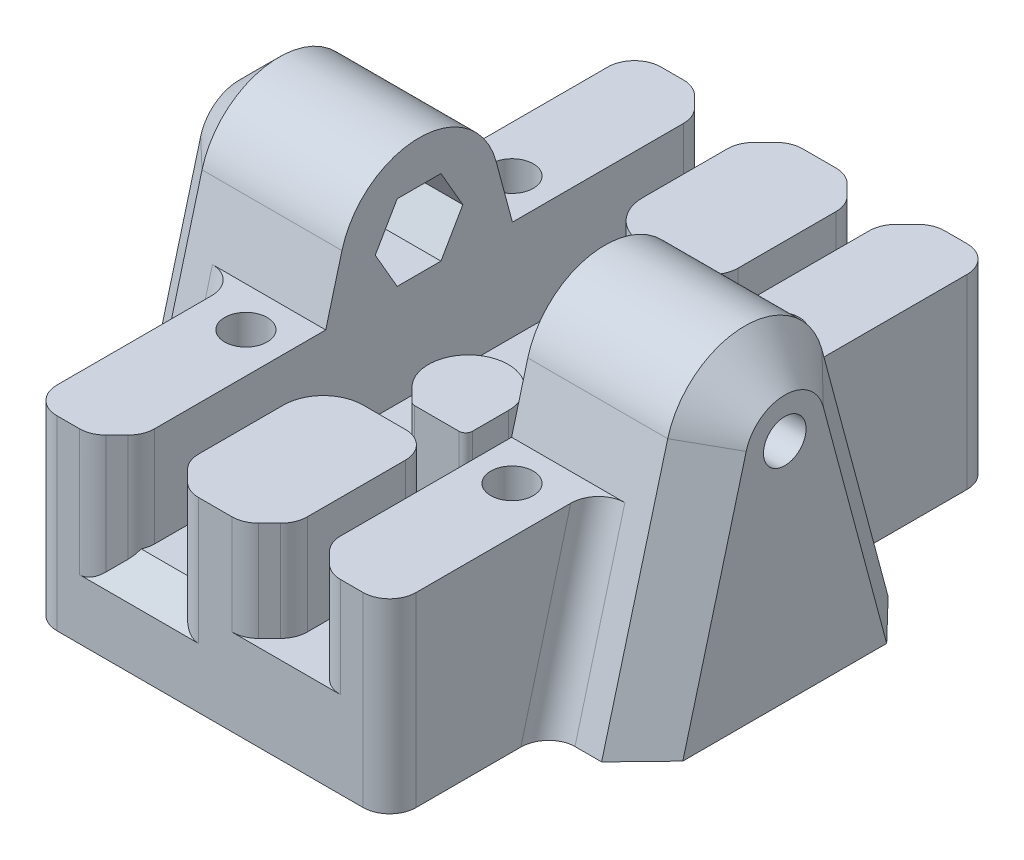
SolidWorks part; units mm, degrees
ref_plane "Front Plane" through (0, 0, 0) normal (0, 0, 1) x (1, 0, 0)
ref_plane "Top Plane" through (0, 0, 0) normal (0, 1, 0) x (1, 0, 0)
ref_plane "Right Plane" through (0, 0, 0) normal (1, 0, 0) x (0, 0, -1)
sketch "Sketch1" plane through (0, 0, 0) normal (0, 1, 0) x (1, 0, 0)
  line L1 (-12, -22.7) -> (12, -22.7)
  line L2 (-13.5, -21.2) -> (-13.5, 21.2)
  line L3 (-12, 22.7) -> (12, 22.7)
  line L4 (13.5, -21.2) -> (13.5, 21.2)
  line L5 (-13.5, -22.7) -> (13.5, 22.7) construction
  line L6 (-13.5, 22.7) -> (13.5, -22.7) construction
  arc A0 (-13.5, 21.2) -> (-12, 22.7) centre (-12, 21.2) cw
  arc A1 (12, 22.7) -> (13.5, 21.2) centre (12, 21.2) cw
  arc A2 (12, -22.7) -> (13.5, -21.2) centre (12, -21.2) ccw
  arc A3 (-12, -22.7) -> (-13.5, -21.2) centre (-12, -21.2) cw
  point P0 (0, 0)
  dimension "D3" = 1.5
  dimension "D1" = 27
  dimension "D2" = 45.4
sketch "Sketch3" plane through (0, 0, 0) normal (1, 0, 0) x (0, 0, -1)
  line L0 (55, 0) -> (-55, 0) construction
  line L1 (0, 55) -> (0, -55) construction
  circle A0 centre (0, 4) radius 5
  dimension "D1" = 10
  dimension "D2" = 4
sketch "Sketch27" plane through (0, 0, 0) normal (0, 1, 0) x (1, 0, 0)
  line L6 (4.6213, 8.6) -> (1.2858, 8.6)
  line L7 (0.9322, 8.4536) -> (0, 7.5213)
  line L8 (5.1213, 5.4) -> (5.1213, 8.1)
  line L12 (1.2858, -8.6) -> (4.6213, -8.6)
  line L13 (5.1213, -8.1) -> (5.1213, -5.4)
  line L14 (0, -7.5213) -> (0.9322, -8.4536)
  line L28 (2.985, -10.5) -> (1.317, -10.5)
  line L29 (1.317, -10.5) -> (1.317, -12.5)
  line L30 (1.317, -12.5) -> (2.485, -12.5)
  line L31 (2.485, -12.5) -> (2.485, -20.5)
  line L32 (2.485, -20.5) -> (-3.683, -20.5)
  line L33 (-3.683, -20.5) -> (-3.683, -22.7)
  line L34 (-3.683, -22.7) -> (4.485, -22.7)
  line L35 (4.485, -22.7) -> (4.485, -12)
  line L44 (6.985, -20.5) -> (6.985, -22.7)
  line L45 (6.985, -22.7) -> (12, -22.7)
  line L46 (13.5, -21.2) -> (13.5, -5.35)
  line L47 (13.5, -5.35) -> (11.3, -5.35)
  line L48 (11.3, -5.35) -> (11.3, -6.4293)
  line L49 (6.985, -7.687) -> (6.985, -12.313)
  line L50 (11.3, -13.5707) -> (11.3, -20.5)
  line L51 (11.3, -20.5) -> (6.985, -20.5)
  line L60 (6.985, 12.313) -> (6.985, 7.687)
  line L61 (11.3, 6.4293) -> (11.3, 5.35)
  line L62 (11.3, 5.35) -> (13.5, 5.35)
  line L63 (13.5, 5.35) -> (13.5, 21.2)
  line L64 (12, 22.7) -> (6.985, 22.7)
  line L65 (6.985, 22.7) -> (6.985, 20.5)
  line L66 (6.985, 20.5) -> (11.3, 20.5)
  line L67 (11.3, 20.5) -> (11.3, 13.5707)
  line L68 (1.317, 12.5) -> (-3.683, 12.5)
  line L69 (-3.683, 12.5) -> (-3.683, 10.5)
  line L70 (-3.683, 10.5) -> (1.317, 10.5)
  line L71 (1.317, 10.5) -> (1.317, 12.5)
  line L84 (2.485, 12.5) -> (1.317, 12.5)
  line L85 (1.317, 12.5) -> (1.317, 10.5)
  line L86 (1.317, 10.5) -> (2.985, 10.5)
  line L87 (4.485, 12) -> (4.485, 22.7)
  line L88 (4.485, 22.7) -> (-3.683, 22.7)
  line L89 (-3.683, 22.7) -> (-3.683, 20.5)
  line L90 (-3.683, 20.5) -> (2.485, 20.5)
  line L91 (2.485, 20.5) -> (2.485, 12.5)
  line L92 (1.317, -10.5) -> (-3.683, -10.5)
  line L93 (-3.683, -10.5) -> (-3.683, -12.5)
  line L94 (-3.683, -12.5) -> (1.317, -12.5)
  line L95 (1.317, -12.5) -> (1.317, -10.5)
  line L110 (-6.985, -12.5) -> (-6.985, -7.687)
  line L111 (-11.3, -6.4293) -> (-11.3, -5.35)
  line L112 (-11.3, -5.35) -> (-13.5, -5.35)
  line L113 (-13.5, -5.35) -> (-13.5, -21.2)
  line L114 (-12, -22.7) -> (-6.985, -22.7)
  line L115 (-6.985, -22.7) -> (-6.985, -20.5)
  line L116 (-6.985, -20.5) -> (-11.3, -20.5)
  line L117 (-11.3, -20.5) -> (-11.3, -13.5707)
  line L118 (-7.1382, -12.5) -> (-6.985, -12.5)
  line L128 (-6.985, 20.5) -> (-6.985, 22.7)
  line L129 (-6.985, 22.7) -> (-12, 22.7)
  line L130 (-13.5, 21.2) -> (-13.5, 5.35)
  line L131 (-13.5, 5.35) -> (-11.3, 5.35)
  line L132 (-11.3, 5.35) -> (-11.3, 6.4293)
  line L133 (-6.985, 7.687) -> (-6.985, 12.5)
  line L134 (-6.985, 12.5) -> (-7.1382, 12.5)
  line L135 (-11.3, 13.5707) -> (-11.3, 20.5)
  line L136 (-11.3, 20.5) -> (-6.985, 20.5)
  arc A2 (4.485, -12) -> (2.985, -10.5) centre (2.985, -12) ccw
  arc A6 (1.2858, 8.6) -> (0.9322, 8.4536) centre (1.2858, 8.1) ccw
  arc A7 (0, 7.5213) -> (5.1213, 5.4) centre (2.1213, 5.4) ccw
  arc A8 (5.1213, 8.1) -> (4.6213, 8.6) centre (4.6213, 8.1) ccw
  arc A12 (4.6213, -8.6) -> (5.1213, -8.1) centre (4.6213, -8.1) ccw
  arc A13 (5.1213, -5.4) -> (0, -7.5213) centre (2.1213, -5.4) ccw
  arc A14 (0.9322, -8.4536) -> (1.2858, -8.6) centre (1.2858, -8.1) ccw
  arc A16 (2.985, 10.5) -> (4.485, 12) centre (2.985, 12) ccw
  arc A20 (12, -22.7) -> (13.5, -21.2) centre (12, -21.2) ccw
  arc A21 (11.3, -6.4293) -> (6.985, -7.687) centre (10, -10) ccw
  arc A22 (6.985, -12.313) -> (11.3, -13.5707) centre (10, -10) ccw
  arc A26 (6.985, 7.687) -> (11.3, 6.4293) centre (10, 10) ccw
  arc A27 (13.5, 21.2) -> (12, 22.7) centre (12, 21.2) ccw
  arc A28 (11.3, 13.5707) -> (6.985, 12.313) centre (10, 10) ccw
  arc A34 (-6.985, -7.687) -> (-11.3, -6.4293) centre (-10, -10) ccw
  arc A35 (-13.5, -21.2) -> (-12, -22.7) centre (-12, -21.2) ccw
  arc A36 (-11.3, -13.5707) -> (-7.1382, -12.5) centre (-10, -10) ccw
  arc A40 (-12, 22.7) -> (-13.5, 21.2) centre (-12, 21.2) ccw
  arc A41 (-11.3, 6.4293) -> (-6.985, 7.687) centre (-10, 10) ccw
  arc A42 (-7.1382, 12.5) -> (-11.3, 13.5707) centre (-10, 10) ccw
sketch "Sketch29" plane through (0, 0, 0) normal (0, 1, 0) x (1, 0, 0)
  line L1 (-13.5, 22.7) -> (13.5, 22.7)
  line L2 (-13.5, 22.7) -> (-13.5, -22.7)
  line L3 (-13.5, -22.7) -> (13.5, -22.7)
  line L4 (13.5, 22.7) -> (13.5, -22.7)
extrude "Boss-Extrude1" add sketch "Sketch29" along normal blind 6.5
fillet "Fillet1" radius 2 4 edges at (-13.5, 3.25, -22.7) (13.5, 3.25, -22.7) (13.5, 3.25, 22.7) (-13.5, 3.25, 22.7)
sketch "Sketch30" plane through (0, 6.5, 0) normal (0, 1, 0) x (1, 0, 0)
  line L5 (4.485, -22.7) -> (4.485, -12) construction
  line L9 (-3.683, -10.5) -> (-3.683, -12.5) construction
  line L12 (-13.5, 0) -> (13.5, 0) construction
  line L13 (4.485, 22.7) -> (4.485, 10.5)
  line L14 (-11.5, -22.7) -> (11.5, -22.7) construction
  line L15 (-3.683, 10.5) -> (4.485, 10.5)
  line L16 (-3.683, 10.5) -> (-3.683, 22.7)
  line L17 (4.485, -10.5) -> (-3.683, -10.5)
  line L18 (6.985, 22.7) -> (6.985, -22.7)
  line L19 (-6.985, 22.7) -> (-6.985, -22.7)
  line L20 (-3.683, -22.7) -> (4.485, -22.7)
  line L21 (6.985, -22.7) -> (11.5, -22.7)
  line L22 (4.485, 22.7) -> (-3.683, 22.7)
  line L23 (-6.985, 22.7) -> (-11.5, 22.7)
  line L24 (4.6213, 8.6) -> (1.2858, 8.6) construction
  line L25 (0.9322, 8.4536) -> (0, 7.5213) construction
  line L26 (5.1213, 5.4) -> (5.1213, 8.1) construction
  line L27 (0, -7.5213) -> (0.9322, -8.4536) construction
  line L28 (1.2858, -8.6) -> (4.6213, -8.6) construction
  line L29 (5.1213, -8.1) -> (5.1213, -5.4) construction
  line L69 (4.485, -22.7) -> (4.485, -10.5)
  line L73 (-3.683, -10.5) -> (-3.683, -22.7)
  line L80 (11.5, 22.7) -> (-11.5, 22.7)
  line L81 (-13.5, 20.7) -> (-13.5, -20.7)
  line L82 (-11.5, -22.7) -> (11.5, -22.7)
  line L83 (13.5, -20.7) -> (13.5, 20.7)
  line L84 (11.5, 22.7) -> (6.985, 22.7)
  line L85 (-13.5, 20.7) -> (-13.5, -20.7)
  line L86 (-11.5, -22.7) -> (-6.985, -22.7)
  line L87 (13.5, -20.7) -> (13.5, 20.7)
  line L88 (4.6213, 8.6) -> (1.2858, 8.6)
  line L89 (0.9322, 8.4536) -> (0, 7.5213)
  line L90 (5.1213, 5.4) -> (5.1213, 8.1)
  line L91 (0, -7.5213) -> (0.9322, -8.4536)
  line L92 (1.2858, -8.6) -> (4.6213, -8.6)
  line L93 (5.1213, -8.1) -> (5.1213, -5.4)
  arc A2 (1.2858, 8.6) -> (0.9322, 8.4536) centre (1.2858, 8.1) ccw construction
  arc A3 (0, 7.5213) -> (5.1213, 5.4) centre (2.1213, 5.4) ccw construction
  arc A4 (5.1213, 8.1) -> (4.6213, 8.6) centre (4.6213, 8.1) ccw construction
  arc A5 (0.9322, -8.4536) -> (1.2858, -8.6) centre (1.2858, -8.1) ccw construction
  arc A6 (4.6213, -8.6) -> (5.1213, -8.1) centre (4.6213, -8.1) ccw construction
  arc A7 (5.1213, -5.4) -> (0, -7.5213) centre (2.1213, -5.4) ccw construction
  arc A22 (1.2858, 8.6) -> (0.9322, 8.4536) centre (1.2858, 8.1) ccw
  arc A23 (0, 7.5213) -> (5.1213, 5.4) centre (2.1213, 5.4) ccw
  arc A24 (5.1213, 8.1) -> (4.6213, 8.6) centre (4.6213, 8.1) ccw
  arc A25 (0.9322, -8.4536) -> (1.2858, -8.6) centre (1.2858, -8.1) ccw
  arc A26 (4.6213, -8.6) -> (5.1213, -8.1) centre (4.6213, -8.1) ccw
  arc A27 (5.1213, -5.4) -> (0, -7.5213) centre (2.1213, -5.4) ccw
  arc A31 (-11.5, 22.7) -> (-13.5, 20.7) centre (-11.5, 20.7) ccw
  arc A32 (-13.5, -20.7) -> (-11.5, -22.7) centre (-11.5, -20.7) ccw
  arc A33 (11.5, -22.7) -> (13.5, -20.7) centre (11.5, -20.7) ccw
  arc A34 (13.5, 20.7) -> (11.5, 22.7) centre (11.5, 20.7) ccw
  arc A35 (-11.5, 22.7) -> (-13.5, 20.7) centre (-11.5, 20.7) ccw
  arc A36 (-13.5, -20.7) -> (-11.5, -22.7) centre (-11.5, -20.7) ccw
  arc A37 (11.5, -22.7) -> (13.5, -20.7) centre (11.5, -20.7) ccw
  arc A38 (13.5, 20.7) -> (11.5, 22.7) centre (11.5, 20.7) ccw
  dimension "D1" = 0
extrude "Boss-Extrude2" add sketch "Sketch30" along normal blind 7.5
fillet "Fillet2" radius 3 2 edges at (-3.683, 10.25, 10.5) (-3.683, 10.25, -10.5)
chamfer "Chamfer1" distance 2 angle 45 8 edges at (-6.985, 10.25, -22.7) (-3.683, 10.25, -22.7) (4.485, 10.25, -22.7) (4.485, 10.25, 22.7) (-6.985, 10.25, 22.7) (-3.683, 10.25, 22.7)
fillet "Fillet3" radius 2 16 edges at (-6.985, 10.25, 20.7) (-8.985, 10.25, 22.7) (-1.683, 10.25, 22.7) (-3.683, 10.25, 20.7) (4.485, 10.25, 20.7) (2.485, 10.25, 22.7) (6.985, 10.25, 20.7) (8.985, 10.25, 22.7) (6.985, 10.25, -20.7) (8.985, 10.25, -22.7) (4.485, 10.25, -20.7) (2.485, 10.25, -22.7) (-1.683, 10.25, -22.7) (-3.683, 10.25, -20.7) (-6.985, 10.25, -20.7) (-8.985, 10.25, -22.7)
sketch "Sketch31" plane through (0, 14, 0) normal (0, 1, 0) x (1, 0, 0)
  line L1 (-10, -10) -> (10, -10) construction
  line L2 (-10, -10) -> (-10, 10) construction
  line L3 (-10, 10) -> (10, 10) construction
  line L4 (10, -10) -> (10, 10) construction
  line L5 (-10, -10) -> (10, 10) construction
  line L6 (-10, 10) -> (10, -10) construction
  circle A0 centre (10, 10) radius 1.6
  circle A1 centre (10, -10) radius 1.6
  circle A2 centre (-10, -10) radius 1.6
  circle A3 centre (-10, 10) radius 1.6
  point P0 (0, 0)
  dimension "D2" = 3.2
  dimension "D1" = 20
extrude "Cut-Extrude1" cut sketch "Sketch31" against normal through all
sketch "Sketch32" plane through (0, 0, 0) normal (1, 0, 0) x (0, 0, -1)
  line L0 (-22.7, 17) -> (22.7, 17) construction
  line L1 (-20.7, 0) -> (20.7, 0) construction
  line L2 (-22.7, 0) -> (-22.7, 14) construction
  line L3 (22.7, 14) -> (22.7, 0) construction
  line L4 (0, 0) -> (0, 20.1512) construction
  line L6 (-5.7956, 18.5529) -> (-10.7668, 0)
  line L7 (-10.7668, 0) -> (10.7668, 0)
  line L8 (5.7956, 18.5529) -> (10.7668, 0)
  arc A0 (5.7956, 18.5529) -> (-5.7956, 18.5529) centre (0, 17) ccw
  dimension "D3" = 12
  dimension "D1" = 17
  dimension "D2" = 30
sketch "Sketch33" plane through (13.5, 0, 0) normal (1, 0, 0) x (0, 0, -1)
  line L3 (-5.7956, 18.5529) -> (-10.7668, 0)
  line L4 (-10.7668, 0) -> (10.7668, 0)
  line L5 (10.7668, 0) -> (5.7956, 18.5529)
  line L6 (-5.7956, 18.5529) -> (-10.7668, 0)
  line L7 (-10.7668, 0) -> (10.7668, 0)
  line L8 (10.7668, 0) -> (5.7956, 18.5529)
  arc A1 (5.7956, 18.5529) -> (-5.7956, 18.5529) centre (0, 17) ccw
  arc A2 (5.7956, 18.5529) -> (-5.7956, 18.5529) centre (0, 17) ccw
  dimension "D1" = 0
extrude "Boss-Extrude3" add sketch "Sketch33" along normal offset from surface (7.5 mm away) 21 up to plane "Right Plane"
sketch "Sketch34" plane through (-13.5, 0, 0) normal (-1, 0, 0) x (0, 0, 1)
  line L3 (-5.7956, 18.5529) -> (-10.7668, 0)
  line L4 (10.7668, 0) -> (5.7956, 18.5529)
  line L5 (-10.7668, 0) -> (10.7668, 0)
  line L6 (-5.7956, 18.5529) -> (-10.7668, 0)
  line L7 (10.7668, 0) -> (5.7956, 18.5529)
  line L8 (-10.7668, 0) -> (10.7668, 0)
  arc A1 (5.7956, 18.5529) -> (-5.7956, 18.5529) centre (0, 17) ccw
  arc A2 (5.7956, 18.5529) -> (-5.7956, 18.5529) centre (0, 17) ccw
  dimension "D1" = 0
extrude "Boss-Extrude4" add sketch "Sketch34" along normal offset from surface (7.5 mm away) 21 up to plane "Right Plane" offset beyond the face yes
chamfer "Chamfer2" distance 3.5 angle 45 6 edges at (-21, 9.2765, 8.2812) (-21, 23, 0) (-21, 9.2765, -8.2812) (21, 9.2765, 8.2812) (21, 23, 0) (21, 9.2765, -8.2812)
sketch "Sketch35" plane through (-21, 0, 0) normal (-1, 0, 0) x (0, 0, 1)
  circle A0 centre (0, 17) radius 1.6
  arc A1 (2.4148, 17.647) -> (-2.4148, 17.647) centre (0, 17) ccw construction
  dimension "D1" = 3.2
extrude "Cut-Extrude2" cut sketch "Sketch35" against normal through all
sketch "Sketch36" plane through (13.5, 0, 0) normal (-1, 0, 0) x (0, 0, 1)
  line L1 (3.3486, 17) -> (1.6743, 19.9)
  line L2 (1.6743, 19.9) -> (-1.6743, 19.9)
  line L3 (-1.6743, 19.9) -> (-3.3486, 17)
  line L4 (-3.3486, 17) -> (-1.6743, 14.1)
  line L5 (-1.6743, 14.1) -> (1.6743, 14.1)
  line L6 (1.6743, 14.1) -> (3.3486, 17)
  circle A0 centre (0, 17) radius 2.9 construction
  dimension "D1" = 5.8
extrude "Cut-Extrude3" cut sketch "Sketch36" against normal offset from surface 3 and the other way offset from surface 3 up to face at (21, 17, 1.6) other way up to face at (-21, 17, 1.6)
chamfer "Chamfer3" distance 2 angle 45 2 edges
fillet "Fillet5" radius 2 2 edges at (4.485, 10.25, 10.5) (4.485, 10.25, -10.5)
other "Move Face1" flip direction yes face at (21, 17, 1.6) face at (-21, 17, 1.6) offset 0.5 parameters "D1"=0.5
sketch "Sketch37" plane through (13.5, 0, 0) normal (-1, 0, 0) x (0, 0, 1)
  line L10 (-7.0155, 14) -> (7.0155, 14)
  line L18 (7.0155, 14) -> (5.7956, 18.5529)
  line L19 (-5.7956, 18.5529) -> (-7.0155, 14)
  line L20 (-7.0155, 14) -> (7.0155, 14)
  line L28 (7.0155, 14) -> (5.7956, 18.5529)
  line L29 (-5.7956, 18.5529) -> (-7.0155, 14)
  arc A1 (5.7956, 18.5529) -> (-5.7956, 18.5529) centre (0, 17) ccw
  arc A2 (5.7956, 18.5529) -> (-5.7956, 18.5529) centre (0, 17) ccw
  dimension "D1" = 0
extrude "Boss-Extrude5" add sketch "Sketch37" along normal up to surface (6.515 mm away) up to face at (6.985, 10.25, -4.9679)
sketch "Sketch38" plane through (-13.5, 0, 0) normal (1, 0, 0) x (0, 0, -1)
  line L12 (-7.0155, 14) -> (7.0155, 14)
  line L13 (7.0155, 14) -> (5.7956, 18.5529)
  line L14 (-5.7956, 18.5529) -> (-7.0155, 14)
  line L22 (-7.0155, 14) -> (7.0155, 14)
  line L23 (7.0155, 14) -> (5.7956, 18.5529)
  line L24 (-5.7956, 18.5529) -> (-7.0155, 14)
  arc A1 (5.7956, 18.5529) -> (-5.7956, 18.5529) centre (0, 17) ccw
  arc A2 (5.7956, 18.5529) -> (-5.7956, 18.5529) centre (0, 17) ccw
  dimension "D1" = 0
extrude "Boss-Extrude6" add sketch "Sketch38" along normal up to surface (6.515 mm away) up to face at (-6.985, 10.25, 0)
fillet "Fillet6" radius 2 4 edges at (13.5, 7, -8.8911) (13.5, 7, 8.8911) (-13.5, 7, 8.8911) (-13.5, 7, -8.8911)
sketch "Sketch39" plane through (0, 14, 0) normal (0, 1, 0) x (1, 0, 0)
  circle A0 centre (-10, -10) radius 3
  circle A1 centre (10, -10) radius 3
  circle A2 centre (10, 10) radius 3
  circle A3 centre (-10, 10) radius 3
  dimension "D1" = 6
sketch "Sketch40" plane through (6.985, 0, 0) normal (-1, 0, 0) x (0, 0, 1)
  line L1 (-1.6454, 19.85) -> (-3.2909, 17)
  line L2 (-3.2909, 17) -> (-1.6454, 14.15)
  line L3 (-1.6454, 14.15) -> (1.6454, 14.15)
  line L4 (1.6454, 14.15) -> (3.2909, 17)
  line L5 (3.2909, 17) -> (1.6454, 19.85)
  line L7 (1.6454, 19.85) -> (-1.6454, 19.85)
  circle A0 centre (0, 17) radius 2.85 construction
  circle A1 centre (0, 17) radius 1.6 construction
  dimension "D1" = 5.7
extrude "Cut-Extrude4" cut sketch "Sketch40" against normal up to surface and the other way up to surface up to face at (18, 17, 0) other way up to face at (-18, 17, 0)
